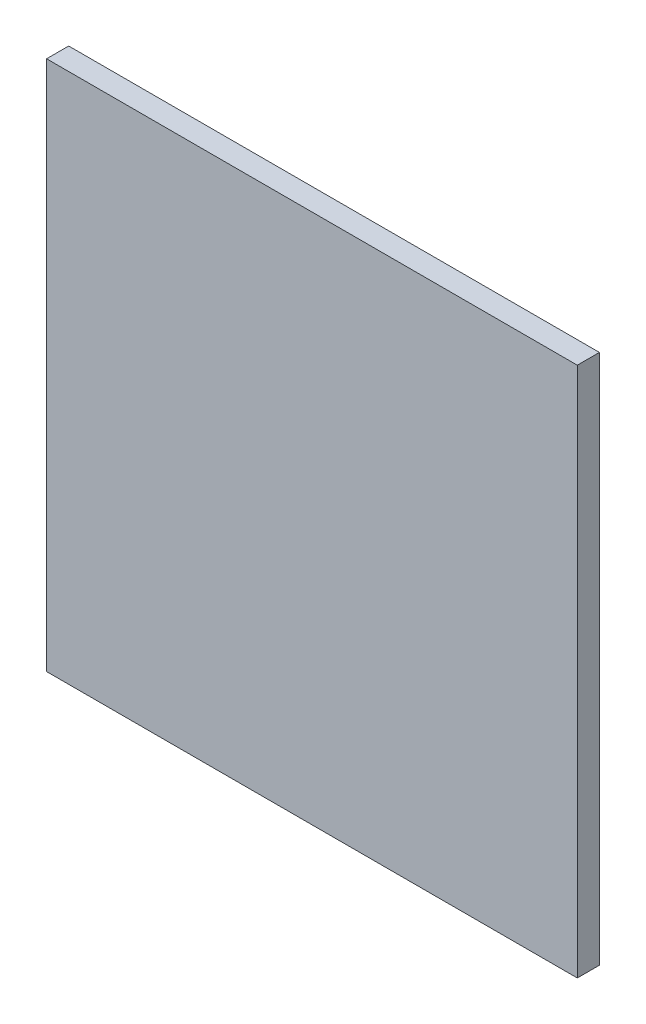
SolidWorks part; units mm, degrees
ref_plane "Front Plane" through (0, 0, 0) normal (0, 0, 1) x (1, 0, 0)
ref_plane "Top Plane" through (0, 0, 0) normal (0, 1, 0) x (1, 0, 0)
ref_plane "Right Plane" through (0, 0, 0) normal (1, 0, 0) x (0, 0, -1)
sketch "Sketch1" plane through (0, 0, 0) normal (0, 0, 1) x (1, 0, 0)
  line L1 (0, 0) -> (76.2, 0)
  line L2 (0, 0) -> (0, 76.2)
  line L3 (0, 76.2) -> (76.2, 76.2)
  line L4 (76.2, 0) -> (76.2, 76.2)
  dimension "D1" = 76.2
  dimension "D2" = 76.2
extrude "Boss-Extrude1" add sketch "Sketch1" along normal blind 3.175
